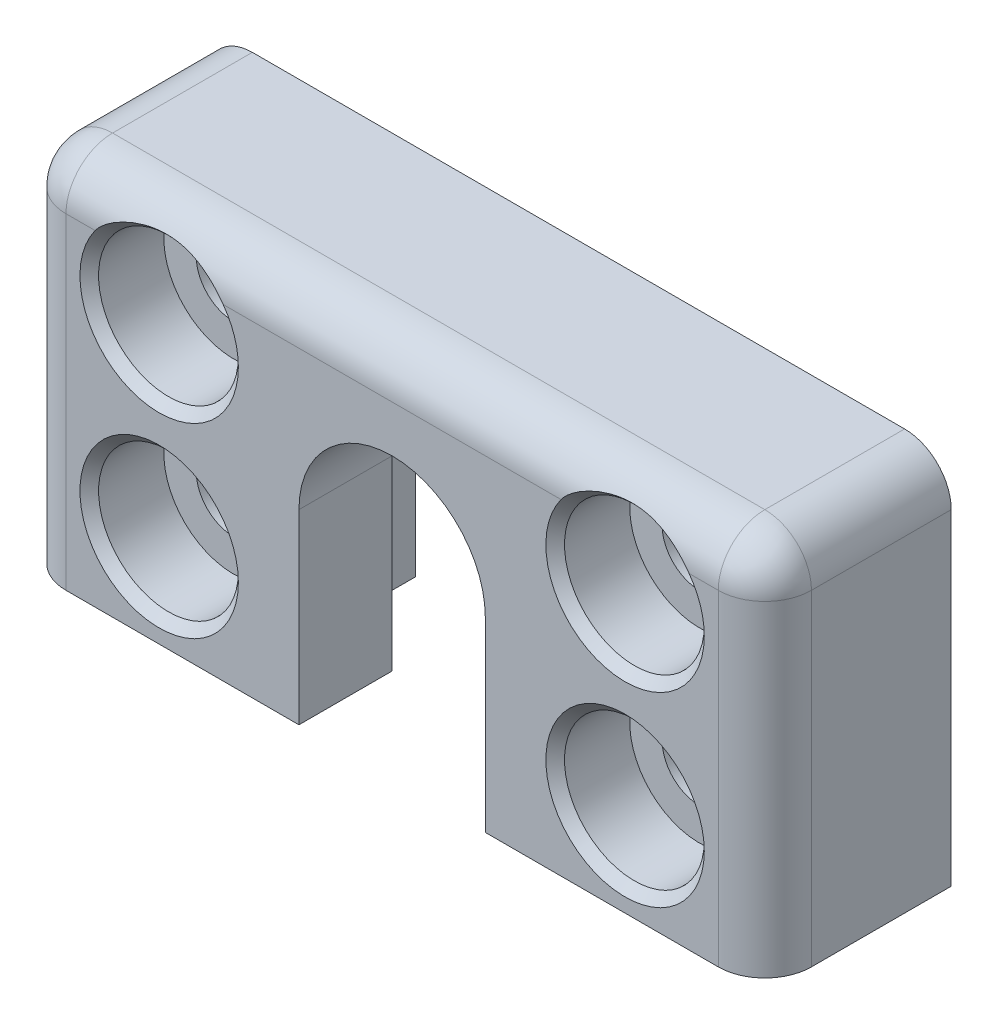
SolidWorks part; units mm, degrees
ref_plane "Front Plane" through (0, 0, 0) normal (0, 0, 1) x (1, 0, 0)
ref_plane "Top Plane" through (0, 0, 0) normal (0, 1, 0) x (1, 0, 0)
ref_plane "Right Plane" through (0, 0, 0) normal (1, 0, 0) x (0, 0, -1)
sketch "Sketch1" plane through (0, 0, 0) normal (0, 0, 1) x (1, 0, 0)
  line L0 (0, 12.7) -> (0, -12.7) construction
  line L1 (-25.4, 12.7) -> (25.4, 12.7)
  line L2 (-25.4, 12.7) -> (-25.4, -12.7)
  line L3 (-25.4, -12.7) -> (25.4, -12.7)
  line L4 (25.4, 12.7) -> (25.4, -12.7)
  line L5 (-25.4, 12.7) -> (25.4, -12.7) construction
  line L6 (-25.4, -12.7) -> (25.4, 12.7) construction
  line L7 (-25.4, 0) -> (25.4, 0) construction
  point P0 (0, 0)
  dimension "D1" = 50.8
  dimension "D2" = 25.4
extrude "Boss-Extrude1" add sketch "Sketch1" against normal blind 12.7
hole_wizard "CBORE for #10 Socket Head Cap Screw1" positions "Sketch3" profile "Sketch2" counterbore size "#10" standard "ANSI Inch" end condition up to next
sketch "Sketch3" plane through (0, 0, 0) normal (0, 0, 1) x (1, 0, 0)
  line L0 (0, 12.7) -> (0, -12.7) construction
  line L1 (25.4, 12.7) -> (-25.4, 12.7) construction
  line L2 (-25.4, -12.7) -> (25.4, -12.7) construction
  line L3 (-25.4, 0) -> (25.3584, 0) construction
  line L4 (-25.4, 12.7) -> (-25.4, -12.7) construction
  line L6 (-15.875, 6.35) -> (-15.875, -6.35) construction
  line L7 (-15.875, -6.35) -> (15.875, -6.35) construction
  line L8 (15.875, -6.35) -> (15.875, 6.35) construction
  line L9 (15.875, 6.35) -> (-15.875, 6.35) construction
  line L12 (-15.875, 6.35) -> (0, 0) construction
  line L13 (0, 0) -> (15.875, -6.35) construction
  point P0 (-15.875, 6.35)
  point P2 (15.875, 6.35)
  point P4 (15.875, -6.35)
  point P6 (-15.875, -6.35)
  dimension "D1" = 15.875
  dimension "D2" = 6.35
sketch "Sketch2" plane through (-15.875, 6.35, 0) normal (1, 0, 0) x (0, -1, 0)
  line L0 (0, 0) -> (0, 12.7)
  line L1 (0, 12.7) -> (2.5527, 12.7)
  line L3 (2.5527, 12.7) -> (2.5527, 5.08)
  line L4 (4.7625, 5.08) -> (2.5527, 5.08)
  line L5 (4.7625, 5.08) -> (4.7625, 0.635)
  line L6 (4.7625, 0.635) -> (5.3975, 0)
  line L7 (5.3975, 0) -> (0, 0)
  line L8 (-4.7625, 0.635) -> (-5.3975, 0) construction
  line L11 (0, -6.35) -> (0, 107.95) construction
  dimension "Thru Hole Dia." = 5.1054
  dimension "Thru Hole Depth" = 12.7
  dimension "C'Bore Dia." = 9.525
  dimension "C'Bore Depth" = 5.08
  dimension "Near C'Sink Dia." = 10.795
  dimension "Near C'Sink Angle" = 90
sketch "Sketch4" plane through (0, 0, 0) normal (0, 0, 1) x (1, 0, 0)
  line L0 (-6.35, 0) -> (-6.35, -12.7)
  line L1 (-25.4, -12.7) -> (25.4, -12.7) construction
  line L2 (6.35, 0) -> (6.35, -12.7)
  line L3 (6.35, -12.7) -> (-6.35, -12.7)
  arc A0 (6.35, 0) -> (-6.35, 0) centre (0, 0) ccw
  dimension "D1" = 6.35
extrude "Cut-Extrude1" cut sketch "Sketch4" against normal up to next
sketch "Sketch5" plane through (0, 0, -12.7) normal (0, 0, -1) x (-1, 0, 0)
  line L0 (-11.1125, 0) -> (-11.1125, -12.7)
  line L1 (-6.35, -12.7) -> (-25.4, -12.7) construction
  line L2 (-11.1125, -12.7) -> (11.1125, -12.7)
  line L3 (25.4, -12.7) -> (6.35, -12.7) construction
  line L4 (11.1125, -12.7) -> (11.1125, 0)
  arc A0 (11.1125, 0) -> (-11.1125, 0) centre (0, 0) ccw
  dimension "D1" = 11.1125
extrude "Cut-Extrude2" cut sketch "Sketch5" against normal blind 6.35
fillet "Fillet1" radius 3.175 5 edges at (0, 12.7, 0) (-25.4, 12.7, -6.35) (25.4, 12.7, -6.35) (25.4, 0, 0) (-25.4, 0, 0)
